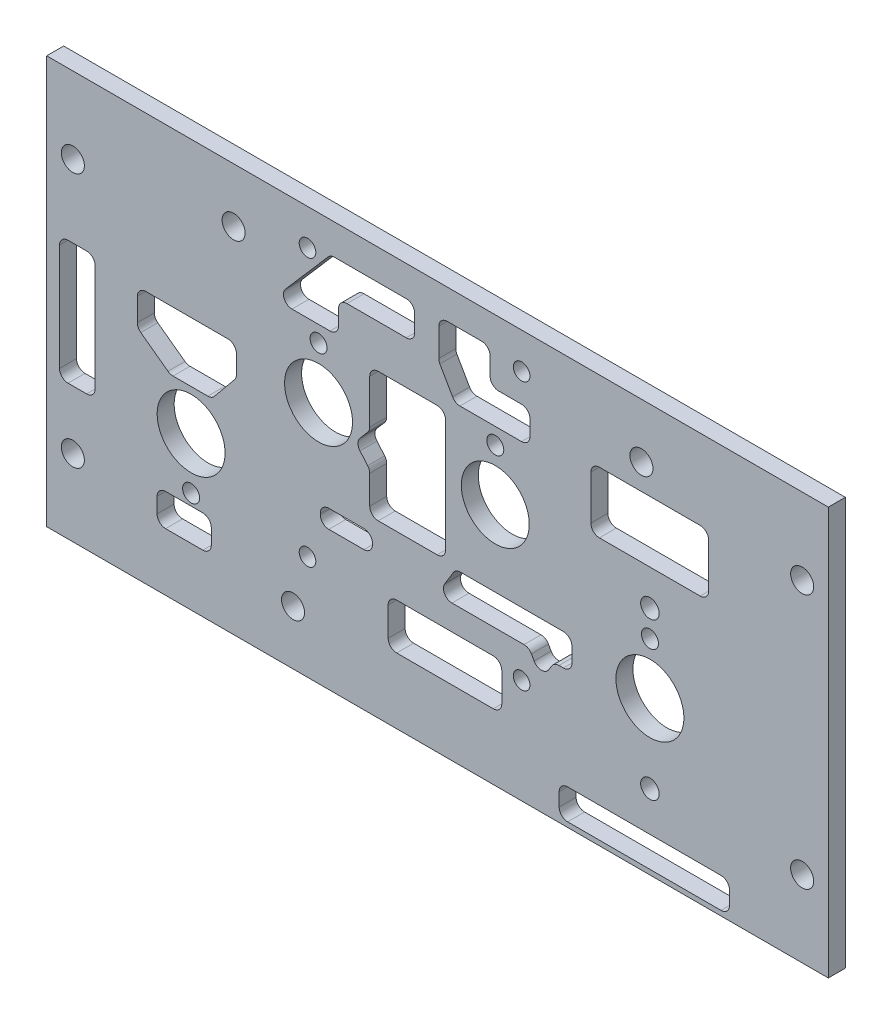
SolidWorks part; units mm, degrees
ref_plane "Front Plane" through (0, 0, 0) normal (0, 0, 1) x (1, 0, 0)
ref_plane "Top Plane" through (0, 0, 0) normal (0, 1, 0) x (1, 0, 0)
ref_plane "Right Plane" through (0, 0, 0) normal (1, 0, 0) x (0, 0, -1)
sketch "Sketch1" plane through (0, 0, 0) normal (0, 0, 1) x (1, 0, 0)
  line L4 (0, 76.2) -> (-146.05, 76.2)
  line L5 (-146.05, 76.2) -> (-146.05, 0)
  line L6 (-146.05, 0) -> (0, 0)
  line L7 (0, 0) -> (0, 76.2)
  line L8 (0, 76.2) -> (-146.05, 76.2)
  line L9 (-146.05, 76.2) -> (-146.05, 0)
  line L10 (-146.05, 0) -> (0, 0)
  line L11 (0, 0) -> (0, 76.2)
  dimension "D1" = 0
extrude "Boss-Extrude1" add sketch "Sketch1" against normal blind 3.175
hole_wizard "1/8 (0.125) Diameter Hole1" positions "Sketch3" profile "Sketch2" hole size "1/8" standard "ANSI Inch" end condition through all
sketch "Sketch3" plane through (0, 0, -3.175) normal (0, 0, -1) x (-1, 0, 0)
  circle A0 centre (95.25, 45.466) radius 9.652 construction
  circle A1 centre (119.0625, 28.575) radius 9.652 construction
  circle A2 centre (62.23, 45.466) radius 9.652 construction
  circle A3 centre (33.3375, 28.575) radius 9.652 construction
  point P0 (95.25, 55.118)
  point P4 (119.0625, 18.923)
  point P8 (62.23, 55.118)
  point P12 (33.3375, 38.227)
sketch "Sketch2" plane through (-95.25, 55.118, -3.175) normal (1, 0, 0) x (0, 1, 0)
  line L0 (0, 0) -> (0, 3.175)
  line L1 (0, 3.175) -> (1.5875, 3.175)
  line L2 (1.5875, 3.175) -> (1.5875, 0)
  line L5 (1.5875, 0) -> (0, 0)
  line L11 (0, -6.35) -> (0, 107.95) construction
  dimension "Thru Hole Dia." = 3.175
  dimension "Thru Hole Depth" = 3.175
hole_wizard "1/2 (0.5) Diameter Hole1" positions "Sketch5" profile "Sketch4" hole size "1/2" standard "ANSI Inch" end condition through all
sketch "Sketch5" plane through (0, 0, -3.175) normal (0, 0, -1) x (-1, 0, 0)
  point P0 (95.25, 45.466)
  point P3 (119.0625, 28.575)
  point P6 (62.23, 45.466)
  point P9 (33.3375, 28.575)
sketch "Sketch4" plane through (-95.25, 45.466, -3.175) normal (1, 0, 0) x (0, 1, 0)
  line L0 (0, 0) -> (0, 3.175)
  line L1 (0, 3.175) -> (6.35, 3.175)
  line L2 (6.35, 3.175) -> (6.35, 0)
  line L5 (6.35, 0) -> (0, 0)
  line L11 (0, -6.35) -> (0, 107.95) construction
  dimension "Thru Hole Dia." = 12.7
  dimension "Thru Hole Depth" = 3.175
hole_wizard "#6 Clearance Hole1" positions "Sketch7" profile "Sketch6" hole size "#6" standard "ANSI Inch" end condition through all
sketch "Sketch7" plane through (0, 0, -3.175) normal (0, 0, -1) x (-1, 0, 0)
  point P0 (141.1605, 61.9125)
  point P3 (141.1605, 14.2875)
  point P6 (4.8895, 61.9125)
  point P10 (4.8895, 14.2875)
  point P13 (111.125, 66.04)
  point P16 (100.015, 10.16)
  point P19 (34.925, 66.04)
sketch "Sketch6" plane through (-141.1605, 61.9125, -3.175) normal (1, 0, 0) x (0, 1, 0)
  line L0 (0, 0) -> (0, 3.175)
  line L1 (0, 3.175) -> (2.1526, 3.175)
  line L2 (2.1526, 3.175) -> (2.1526, 0)
  line L5 (2.1526, 0) -> (0, 0)
  line L11 (0, -6.35) -> (0, 107.95) construction
  dimension "Thru Hole Dia." = 4.3053
  dimension "Thru Hole Depth" = 3.175
hole_wizard "#4 Clearance Hole1" positions "Sketch9" profile "Sketch8" hole size "#4" standard "ANSI Inch" end condition through all
sketch "Sketch9" plane through (0, 0, -3.175) normal (0, 0, -1) x (-1, 0, 0)
  point P0 (33.3375, 43.18)
  point P3 (33.3375, 13.97)
sketch "Sketch8" plane through (-33.3375, 43.18, -3.175) normal (1, 0, 0) x (0, 1, 0)
  line L0 (0, 0) -> (0, 3.175)
  line L1 (0, 3.175) -> (1.7272, 3.175)
  line L2 (1.7272, 3.175) -> (1.7272, 0)
  line L5 (1.7272, 0) -> (0, 0)
  line L11 (0, -6.35) -> (0, 107.95) construction
  dimension "Thru Hole Dia." = 3.4544
  dimension "Thru Hole Depth" = 3.175
sketch "Sketch11" plane through (0, 0, -3.175) normal (0, 0, -1) x (-1, 0, 0)
  line L0 (23.9487, 61.26) -> (42.7833, 61.26)
  line L1 (44.3708, 59.6725) -> (44.3708, 51.4195)
  line L2 (22.3612, 59.6725) -> (22.3612, 51.4195)
  line L3 (23.9487, 49.832) -> (42.7833, 49.832)
  line L4 (64.7801, 70.6544) -> (71.2013, 70.6544)
  line L5 (72.7888, 69.0669) -> (72.7888, 63.8628)
  line L6 (72.5784, 63.0729) -> (70.2067, 58.9385)
  line L7 (68.8296, 58.1409) -> (57.3334, 58.1409)
  line L8 (55.7459, 59.7284) -> (55.7459, 62.5959)
  line L9 (63.1926, 69.0669) -> (63.1926, 65.7709)
  line L10 (61.6051, 64.1834) -> (57.3334, 64.1834)
  line L11 (78.8708, 70.4894) -> (92.27, 70.4894)
  line L12 (93.4697, 69.9417) -> (101.4203, 60.7681)
  line L13 (100.2206, 58.1409) -> (93.1099, 58.1409)
  line L14 (91.5224, 59.7284) -> (91.5224, 62.5791)
  line L15 (89.9349, 64.1666) -> (78.8708, 64.1666)
  line L16 (77.2833, 65.7541) -> (77.2833, 68.9019)
  line L17 (73.0966, 56.1163) -> (84.102, 56.1163)
  line L18 (85.6895, 54.5288) -> (85.6895, 46.3055)
  line L19 (86.0744, 45.2692) -> (87.505, 43.609)
  line L20 (87.5071, 41.5388) -> (86.0723, 39.8671)
  line L21 (85.6895, 38.8332) -> (85.6895, 33.5149)
  line L22 (84.102, 31.9274) -> (73.0966, 31.9274)
  line L23 (71.5091, 33.5149) -> (71.5091, 54.5288)
  line L24 (49.4951, 31.3075) -> (68.7282, 31.3075)
  line L25 (70.0828, 30.5478) -> (71.681, 27.9323)
  line L26 (70.3264, 25.517) -> (56.8566, 25.517)
  line L27 (55.4728, 24.7074) -> (54.969, 23.8112)
  line L28 (52.2305, 23.7613) -> (51.6843, 24.6551)
  line L29 (50.3297, 25.4149) -> (49.4951, 25.4149)
  line L30 (47.9076, 27.0024) -> (47.9076, 29.72)
  line L31 (138.5892, 48.3487) -> (142.062, 48.3487)
  line L32 (143.6495, 46.7612) -> (143.6495, 26.8106)
  line L33 (142.062, 25.2231) -> (138.5892, 25.2231)
  line L34 (137.0017, 26.8106) -> (137.0017, 46.7612)
  line L35 (112.188, 47.3287) -> (127.5281, 47.3287)
  line L36 (129.1156, 45.7412) -> (129.1156, 41.4887)
  line L37 (128.4662, 40.2081) -> (123.3903, 36.4895)
  line L38 (122.4521, 36.1826) -> (115.9411, 36.1826)
  line L39 (114.714, 36.7629) -> (110.9609, 41.3351)
  line L40 (110.6005, 42.3423) -> (110.6005, 45.7412)
  line L41 (20.051, 6.572) -> (48.7123, 6.572)
  line L42 (50.2998, 4.9845) -> (50.2998, 2.5039)
  line L43 (48.7123, 0.9164) -> (20.051, 0.9164)
  line L44 (18.4635, 2.5039) -> (18.4635, 4.9845)
  line L45 (116.8817, 16.8216) -> (123.8316, 16.8216)
  line L46 (125.4191, 15.2341) -> (125.4191, 12.383)
  line L47 (123.8316, 10.7955) -> (116.8817, 10.7955)
  line L48 (115.2942, 12.383) -> (115.2942, 15.2341)
  line L49 (86.7653, 29.3428) -> (93.3373, 29.3428)
  line L50 (94.9248, 27.7553) -> (94.9248, 27.5241)
  line L51 (85.1778, 27.7553) -> (85.1778, 27.5241)
  line L52 (86.7653, 25.9366) -> (93.3373, 25.9366)
  line L53 (62.6019, 20.8228) -> (80.6593, 20.8228)
  line L54 (82.2468, 19.2353) -> (82.2468, 13.8534)
  line L55 (61.0144, 19.2353) -> (61.0144, 13.8534)
  line L56 (62.6019, 12.2659) -> (80.6593, 12.2659)
  arc A0 (63.1926, 65.7709) -> (61.6051, 64.1834) centre (61.6051, 65.7709) cw
  arc A1 (64.7801, 70.6544) -> (63.1926, 69.0669) centre (64.7801, 69.0669) ccw
  arc A2 (71.2013, 70.6544) -> (72.7888, 69.0669) centre (71.2013, 69.0669) cw
  arc A3 (72.7888, 63.8628) -> (72.5784, 63.0729) centre (71.2013, 63.8628) cw
  arc A4 (70.2067, 58.9385) -> (68.8296, 58.1409) centre (68.8296, 59.7284) cw
  arc A5 (57.3334, 58.1409) -> (55.7459, 59.7284) centre (57.3334, 59.7284) cw
  arc A6 (55.7459, 62.5959) -> (57.3334, 64.1834) centre (57.3334, 62.5959) cw
  arc A7 (101.4203, 60.7681) -> (100.2206, 58.1409) centre (100.2206, 59.7284) cw
  arc A8 (93.1099, 58.1409) -> (91.5224, 59.7284) centre (93.1099, 59.7284) cw
  arc A9 (91.5224, 62.5791) -> (89.9349, 64.1666) centre (89.9349, 62.5791) ccw
  arc A10 (92.27, 70.4894) -> (93.4697, 69.9417) centre (92.27, 68.9019) cw
  arc A11 (78.8708, 70.4894) -> (77.2833, 68.9019) centre (78.8708, 68.9019) ccw
  arc A12 (78.8708, 64.1666) -> (77.2833, 65.7541) centre (78.8708, 65.7541) cw
  arc A13 (73.0966, 31.9274) -> (71.5091, 33.5149) centre (73.0966, 33.5149) cw
  arc A14 (85.6895, 33.5149) -> (84.102, 31.9274) centre (84.102, 33.5149) cw
  arc A15 (86.0723, 39.8671) -> (85.6895, 38.8332) centre (87.277, 38.8332) ccw
  arc A16 (85.6895, 46.3055) -> (86.0744, 45.2692) centre (87.277, 46.3055) ccw
  arc A17 (87.505, 43.609) -> (87.5071, 41.5388) centre (86.3024, 42.5727) cw
  arc A18 (84.102, 56.1163) -> (85.6895, 54.5288) centre (84.102, 54.5288) cw
  arc A19 (73.0966, 56.1163) -> (71.5091, 54.5288) centre (73.0966, 54.5288) ccw
  arc A20 (49.4951, 25.4149) -> (47.9076, 27.0024) centre (49.4951, 27.0024) cw
  arc A21 (51.6843, 24.6551) -> (50.3297, 25.4149) centre (50.3297, 23.8274) ccw
  arc A22 (54.969, 23.8112) -> (52.2305, 23.7613) centre (53.5851, 24.589) cw
  arc A23 (56.8566, 25.517) -> (55.4728, 24.7074) centre (56.8566, 23.9295) ccw
  arc A24 (71.681, 27.9323) -> (70.3264, 25.517) centre (70.3264, 27.1045) cw
  arc A25 (68.7282, 31.3075) -> (70.0828, 30.5478) centre (68.7282, 29.72) cw
  arc A26 (49.4951, 31.3075) -> (47.9076, 29.72) centre (49.4951, 29.72) ccw
  arc A28 (138.5892, 25.2231) -> (137.0017, 26.8106) centre (138.5892, 26.8106) cw
  arc A29 (143.6495, 26.8106) -> (142.062, 25.2231) centre (142.062, 26.8106) cw
  arc A30 (142.062, 48.3487) -> (143.6495, 46.7612) centre (142.062, 46.7612) cw
  arc A31 (138.5892, 48.3487) -> (137.0017, 46.7612) centre (138.5892, 46.7612) ccw
  arc A32 (110.9609, 41.3351) -> (110.6005, 42.3423) centre (112.188, 42.3423) cw
  arc A33 (115.9411, 36.1826) -> (114.714, 36.7629) centre (115.9411, 37.7701) cw
  arc A34 (123.3903, 36.4895) -> (122.4521, 36.1826) centre (122.4521, 37.7701) cw
  arc A35 (129.1156, 41.4887) -> (128.4662, 40.2081) centre (127.5281, 41.4887) cw
  arc A36 (127.5281, 47.3287) -> (129.1156, 45.7412) centre (127.5281, 45.7412) cw
  arc A37 (112.188, 47.3287) -> (110.6005, 45.7412) centre (112.188, 45.7412) ccw
  arc A38 (20.051, 0.9164) -> (18.4635, 2.5039) centre (20.051, 2.5039) cw
  arc A39 (50.2998, 2.5039) -> (48.7123, 0.9164) centre (48.7123, 2.5039) cw
  arc A40 (48.7123, 6.572) -> (50.2998, 4.9845) centre (48.7123, 4.9845) cw
  arc A41 (20.051, 6.572) -> (18.4635, 4.9845) centre (20.051, 4.9845) ccw
  arc A42 (123.8316, 16.8216) -> (125.4191, 15.2341) centre (123.8316, 15.2341) cw
  arc A43 (125.4191, 12.383) -> (123.8316, 10.7955) centre (123.8316, 12.383) cw
  arc A44 (116.8817, 10.7955) -> (115.2942, 12.383) centre (116.8817, 12.383) cw
  arc A45 (116.8817, 16.8216) -> (115.2942, 15.2341) centre (116.8817, 15.2341) ccw
  arc A46 (42.7833, 61.26) -> (44.3708, 59.6725) centre (42.7833, 59.6725) cw
  arc A47 (44.3708, 51.4195) -> (42.7833, 49.832) centre (42.7833, 51.4195) cw
  arc A48 (22.3612, 51.4195) -> (23.9487, 49.832) centre (23.9487, 51.4195) ccw
  arc A49 (23.9487, 61.26) -> (22.3612, 59.6725) centre (23.9487, 59.6725) ccw
  arc A50 (93.3373, 29.3428) -> (94.9248, 27.7553) centre (93.3373, 27.7553) cw
  arc A51 (94.9248, 27.5241) -> (93.3373, 25.9366) centre (93.3373, 27.5241) cw
  arc A52 (85.1778, 27.5241) -> (86.7653, 25.9366) centre (86.7653, 27.5241) ccw
  arc A53 (86.7653, 29.3428) -> (85.1778, 27.7553) centre (86.7653, 27.7553) ccw
  arc A54 (80.6593, 20.8228) -> (82.2468, 19.2353) centre (80.6593, 19.2353) cw
  arc A55 (82.2468, 13.8534) -> (80.6593, 12.2659) centre (80.6593, 13.8534) cw
  arc A56 (61.0144, 13.8534) -> (62.6019, 12.2659) centre (62.6019, 13.8534) ccw
  arc A57 (62.6019, 20.8228) -> (61.0144, 19.2353) centre (62.6019, 19.2353) ccw
  circle A58 centre (57.3085, 69.5024) radius 1.55
  circle A59 centre (97.3164, 69.5024) radius 1.55
  circle A60 centre (57.3085, 19.5082) radius 1.55
  circle A61 centre (97.3164, 19.5082) radius 1.55
  dimension "D1" = 1.5875
  dimension "D2" = 1.5875
  dimension "D3" = 1.5875
  dimension "D4" = 1.5875
  dimension "D5" = 3.1
  dimension "D6" = 1.5875
  dimension "D7" = 1.5875
  dimension "D8" = 1.5875
  dimension "D9" = 1.5875
  dimension "D10" = 1.5875
  dimension "D11" = 3.1
  dimension "D12" = 3.1
  dimension "D13" = 3.1
extrude "Backlighting LED Holes" cut sketch "Sketch11" against normal through all
